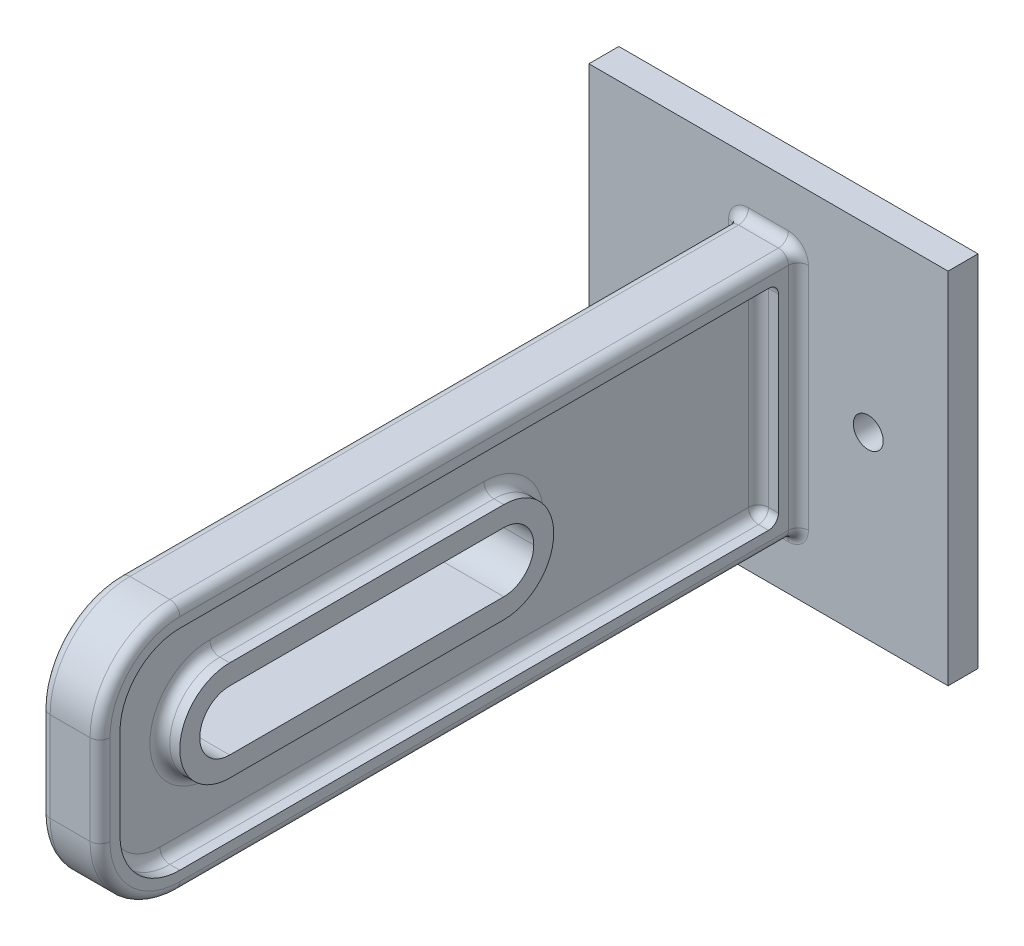
SolidWorks part; units mm, degrees
ref_plane "Front Plane" through (0, 0, 0) normal (0, 0, 1) x (1, 0, 0)
ref_plane "Top Plane" through (0, 0, 0) normal (0, 1, 0) x (1, 0, 0)
ref_plane "Right Plane" through (0, 0, 0) normal (1, 0, 0) x (0, 0, -1)
sketch "Sketch1" plane through (0, 0, 0) normal (0, 0, 1) x (1, 0, 0)
  line L1 (-18, 18) -> (18, 18)
  line L2 (-18, 18) -> (-18, -18)
  line L3 (-18, -18) -> (18, -18)
  line L4 (18, 18) -> (18, -18)
  line L5 (-18, 18) -> (18, -18) construction
  line L6 (-18, -18) -> (18, 18) construction
  point P0 (0, 0)
  dimension "D1" = 36
  dimension "D2" = 36
extrude "Boss-Extrude1" add sketch "Sketch1" along normal blind 3
sketch "Sketch2" plane through (0, 0, 3) normal (0, 0, 1) x (1, 0, 0)
  line L0 (-18, 0) -> (18, 0) construction
  line L1 (-18, 18) -> (-18, -18) construction
  line L2 (18, -18) -> (18, 18) construction
  line L3 (0, 18) -> (0, -18) construction
  line L4 (18, 18) -> (-18, 18) construction
  line L5 (-18, -18) -> (18, -18) construction
  circle A0 centre (-10, 0) radius 1.5
  circle A1 centre (10, 0) radius 1.5
  dimension "D1" = 3
  dimension "D2" = 20
extrude "Cut-Extrude1" cut sketch "Sketch2" against normal blind 3
sketch "Sketch3" plane through (0, 0, 3) normal (0, 0, 1) x (1, 0, 0)
  line L1 (-3, 12.5) -> (3, 12.5)
  line L2 (-3, 12.5) -> (-3, -12.5)
  line L3 (-3, -12.5) -> (3, -12.5)
  line L4 (3, 12.5) -> (3, -12.5)
  line L5 (-3, 12.5) -> (3, -12.5) construction
  line L6 (-3, -12.5) -> (3, 12.5) construction
  point P0 (0, 0)
  dimension "D1" = 6
  dimension "D2" = 25
extrude "Boss-Extrude2" add sketch "Sketch3" along normal blind 70
sketch "Sketch4" plane through (3, 0, 0) normal (1, 0, 0) x (0, 0, -1)
  line L0 (-73, 0) -> (-3, 0) construction
  line L1 (-63, 3) -> (-29.5248, 3)
  line L2 (-63, 3) -> (-63, -3)
  line L3 (-63, -3) -> (-29.5248, -3)
  line L4 (-29.5248, 3) -> (-29.5248, -3)
  line L7 (-73, -12.5) -> (-73, 12.5) construction
  line L8 (-3, -12.5) -> (-3, 12.5) construction
  point P11 (0, 0)
  point P12 (-47.4055, -0.5274)
  dimension "D1" = 6
  dimension "D2" = 10
extrude "Cut-Extrude2" cut sketch "Sketch4" against normal blind 70
fillet "Fillet1" radius 3 4 edges at (0, -3, 63) (0, 3, 63) (0, 3, 29.5248) (0, -3, 29.5248)
fillet "Fillet2" radius 8 2 edges at (0, -12.5, 73) (0, 12.5, 73)
sketch "Sketch6" plane through (3, 0, 0) normal (1, 0, 0) x (0, 0, -1)
  line L56 (-65, -10.5) -> (-5, -10.5)
  line L57 (-5, -10.5) -> (-5, 10.5)
  line L58 (-5, 10.5) -> (-65, 10.5)
  line L59 (-71, 4.5) -> (-71, -4.5)
  line L60 (-65, -10.5) -> (-5, -10.5)
  line L61 (-5, -10.5) -> (-5, 10.5)
  line L62 (-5, 10.5) -> (-65, 10.5)
  line L63 (-71, 4.5) -> (-71, -4.5)
  line L71 (-32.5248, 5) -> (-60, 5)
  line L72 (-60, -5) -> (-32.5248, -5)
  line L73 (-32.5248, 5) -> (-60, 5)
  line L74 (-60, -5) -> (-32.5248, -5)
  arc A28 (-71, -4.5) -> (-65, -10.5) centre (-65, -4.5) ccw
  arc A29 (-65, 10.5) -> (-71, 4.5) centre (-65, 4.5) ccw
  arc A30 (-71, -4.5) -> (-65, -10.5) centre (-65, -4.5) ccw
  arc A31 (-65, 10.5) -> (-71, 4.5) centre (-65, 4.5) ccw
  arc A46 (-32.5248, -5) -> (-27.5248, 0) centre (-32.5248, 0) ccw
  arc A47 (-27.5248, 0) -> (-32.5248, 5) centre (-32.5248, 0) ccw
  arc A48 (-60, 5) -> (-65, 0) centre (-60, 0) ccw
  arc A49 (-65, 0) -> (-60, -5) centre (-60, 0) ccw
  arc A50 (-32.5248, -5) -> (-27.5248, 0) centre (-32.5248, 0) ccw
  arc A51 (-27.5248, 0) -> (-32.5248, 5) centre (-32.5248, 0) ccw
  arc A52 (-60, 5) -> (-65, 0) centre (-60, 0) ccw
  arc A53 (-65, 0) -> (-60, -5) centre (-60, 0) ccw
  dimension "D1" = 2
  dimension "D2" = 2
extrude "Cut-Extrude3" cut sketch "Sketch6" against normal blind 2
mirror "Mirror3" about plane through (0, 0, 0) normal (1, 0, 0) of "Cut-Extrude3"
fillet "Fillet3" radius 1 10 edges at (-1, 10.5, 35) (-1, 8.7426, 69.2426) (-1, -10.5, 35) (-1, -8.7426, 69.2426) (-3, 10.5, 35) (-3, 8.7426, 69.2426) (-3, -10.5, 35) (-3, -8.7426, 69.2426) (-1, 0, 71) (-3, 0, 71)
fillet "Fillet4" radius 1 5 edges at (-2.7071, -10.7929, 5) (-1.2929, -10.2071, 5) (-2.7071, 10.7929, 5) (-1.2929, 10.2071, 5) (-1, 0, 5)
fillet "Fillet5" radius 1 5 edges at (-3, -12.5, 34) (-3, -10.1569, 70.6569) (-3, 0, 73) (-3, 10.1569, 70.6569) (-3, 12.5, 34)
fillet "Fillet6" radius 1 4 edges at (-1, 0, 27.5248) (-1, -5, 46.2624) (-1, 0, 65) (-1, 5, 46.2624)
fillet "Fillet7" radius 1 5 edges at (1, -10.5, 35) (1, -8.7426, 69.2426) (1, 0, 71) (1, 8.7426, 69.2426) (1, 10.5, 35)
fillet "Fillet8" radius 1 5 edges at (2.5, -10.5, 5) (1.2929, -10.2071, 5) (2.5, 10.5, 5) (1.2929, 10.2071, 5) (1, 0, 5)
fillet "Fillet10" radius 1 5 edges at (3, 12.5, 34) (3, 10.1569, 70.6569) (3, 0, 73) (3, -10.1569, 70.6569) (3, -12.5, 34)
fillet "Fillet11" radius 1 12 edges at (2.7071, -12.2071, 3) (0, -12.5, 3) (-2.7071, -12.2071, 3) (-3, 0, 3) (-2.7071, 12.2071, 3) (0, 12.5, 3) (2.7071, 12.2071, 3) (1, 0, 65) (1, 5, 46.2624) (1, 0, 27.5248) (3, 0, 3) (1, -5, 46.2624)
